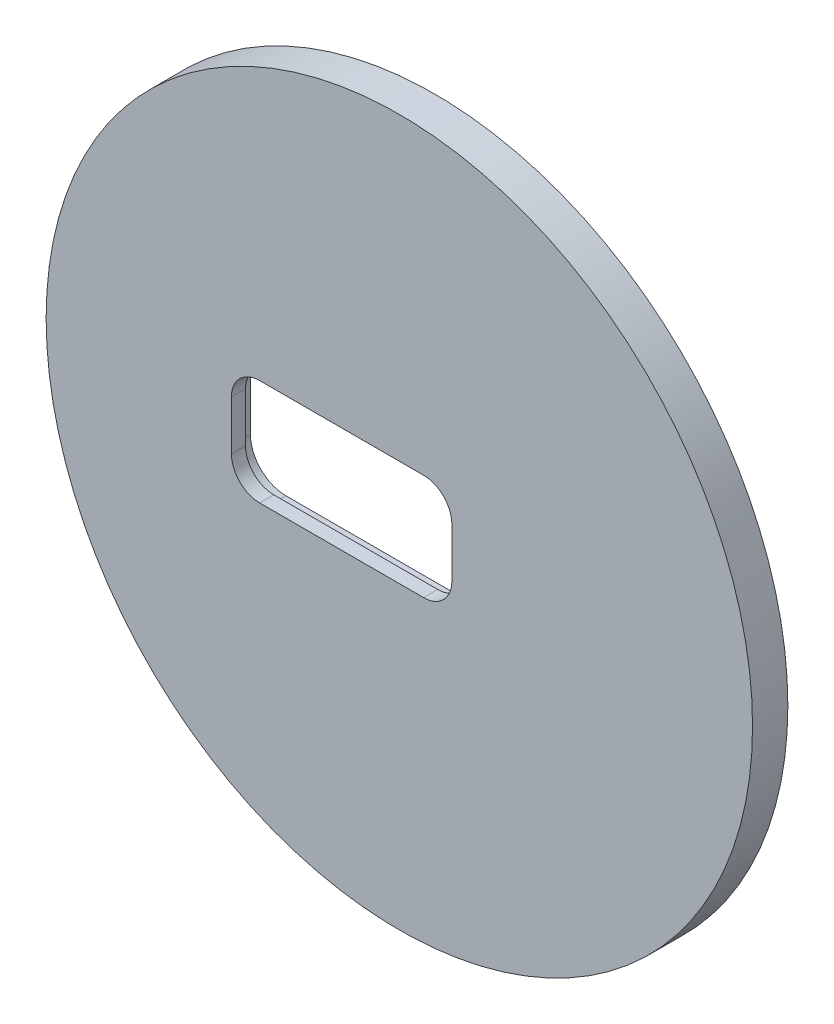
SolidWorks part; units mm, degrees
ref_plane "Front Plane" through (0, 0, 0) normal (0, 0, 1) x (1, 0, 0)
ref_plane "Top Plane" through (0, 0, 0) normal (0, 1, 0) x (1, 0, 0)
ref_plane "Right Plane" through (0, 0, 0) normal (1, 0, 0) x (0, 0, -1)
sketch "Sketch2" plane through (0, 0, 0) normal (0, 0, 1) x (1, 0, 0)
  line L1 (-33.114, 12.365) -> (12.37, 12.365)
  line L2 (-33.114, 12.365) -> (-33.114, -12.435)
  line L3 (-33.114, -12.435) -> (12.37, -12.435)
  line L4 (12.37, 12.365) -> (12.37, -12.435)
  line L5 (-33.114, 12.365) -> (12.37, -12.435) construction
  line L6 (-33.114, -12.435) -> (12.37, 12.365) construction
  line L11 (-30.184, 9.49) -> (9.44, -9.56) construction
  line L12 (-30.184, -9.56) -> (9.44, 9.49) construction
  circle A1 centre (0, 0) radius 3
  point P1 (-10.372, -0.035)
  point P4 (-10.372, -0.035)
  dimension "D1" = 12.37
  dimension "D2" = 6
  dimension "D6" = 39.624
  dimension "D3" = 45.484
  dimension "D4" = 24.8
  dimension "D5" = 19.05
sketch "Sketch3" plane through (0, 0, 0) normal (0, 0, 1) x (1, 0, 0)
  line L1 (-40.5854, 18.7981) -> (19.8414, 18.7981)
  line L2 (-40.5854, 18.7981) -> (-40.5854, -18.8681)
  line L3 (-40.5854, -18.8681) -> (19.8414, -18.8681)
  line L4 (19.8414, 18.7981) -> (19.8414, -18.8681)
  line L5 (-40.5854, 18.7981) -> (19.8414, -18.8681) construction
  line L6 (-40.5854, -18.8681) -> (19.8414, 18.7981) construction
  circle A0 centre (0, 0) radius 63.5
  circle A1 centre (0, 0) radius 57.15
  point P4 (-10.372, -0.035)
  dimension "D1" = 127
  dimension "D2" = 114.3
extrude "Boss-Extrude1" add sketch "Sketch3" along normal blind 6.35 contours A1 | A0 A1 | L2 L1 L4 L3 region at (-61.7039, 0, 0) region at (-55.5336, 0, 0)
extrude "Cut-Extrude1" cut sketch "Sketch2" along normal blind 3.81 contours L4 L1 L2 L3 A1 | A1 | A1 region at (-10.6387, -0.0359, 0) region at (0, 0, 0)
fillet "Fillet1" radius 6.35 4 edges at (-33.114, 12.365, 1.905) (12.37, 12.365, 1.905) (-33.114, -12.435, 1.905) (12.37, -12.435, 1.905)
sketch "Sketch6" plane through (0, 0, 0) normal (0, 0, 1) x (1, 0, 0)
  line L1 (-30.184, 9.49) -> (9.44, 9.49)
  line L2 (-30.184, 9.49) -> (-30.184, -9.56)
  line L3 (-30.184, -9.56) -> (9.44, -9.56)
  line L4 (9.44, 9.49) -> (9.44, -9.56)
  line L5 (-30.184, 9.49) -> (9.44, -9.56) construction
  line L6 (-30.184, -9.56) -> (9.44, 9.49) construction
  point P0 (-10.372, -0.035)
extrude "Cut-Extrude2" cut sketch "Sketch6" along normal blind 6.35
fillet "Fillet2" radius 5.08 4 edges at (-30.184, -9.56, 5.08) (-30.184, 9.49, 5.08) (9.44, 9.49, 5.08) (9.44, -9.56, 5.08)
extrude "Cut-Extrude4" cut sketch "Sketch3<4>" along normal blind 3.81 contours A1 L1 L4 L3 L2 region at (-55.5336, 0, 0)
sketch "Sketch3<4>" plane through (0, 0, 0) normal (0, 0, 1) x (1, 0, 0) same geometry as "Sketch3"
fillet "Fillet3" radius 5.08 4 edges at (19.8414, -18.8681, 1.905) (19.8414, 18.7981, 1.905) (-40.5854, -18.8681, 1.905) (-40.5854, 18.7981, 1.905)
